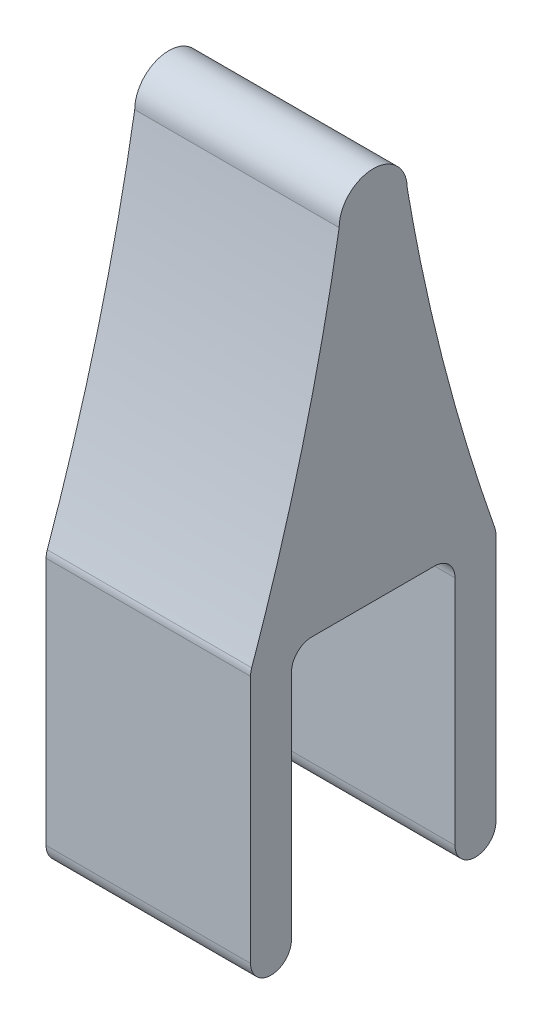
SolidWorks part; units mm, degrees
ref_plane "Front Plane" through (0, 0, 0) normal (0, 0, 1) x (1, 0, 0)
ref_plane "Top Plane" through (0, 0, 0) normal (0, 1, 0) x (1, 0, 0)
ref_plane "Right Plane" through (0, 0, 0) normal (1, 0, 0) x (0, 0, -1)
sketch "Sketch1" plane through (0, 0, 0) normal (1, 0, 0) x (0, 0, -1)
  line L0 (-7.62, 0) -> (-11.43, 0)
  line L1 (-11.43, 0) -> (-11.43, 25.4)
  line L2 (0, -1000) -> (0, 49000) construction
  line L3 (-11.43, 25.4) -> (11.43, 25.4) construction
  line L4 (-7.62, 0) -> (-7.62, 25.4)
  line L5 (-7.62, 25.4) -> (7.62, 25.4)
  line L6 (7.62, 0) -> (7.62, 25.4)
  line L7 (11.43, 0) -> (11.43, 25.4)
  line L8 (7.62, 0) -> (11.43, 0)
  arc A0 (3.175, 57.15) -> (-3.175, 57.15) centre (0, 57.15) ccw
  spline S0 degree 2 poles (-11.43, 25.4) (-5.9489, 40.9005) (-3.175, 57.15) knots 0 0 0 1 1 1
  spline S1 degree 2 poles (11.43, 25.4) (5.9489, 40.9005) (3.175, 57.15) knots 0 0 0 1 1 1
  point P10 (0, 25.4)
  point P12 (0, 25.4)
  point P14 (-8.89, 38.9586)
  point P16 (-6.9566, 46.4492)
  point P18 (-11.0213, 28.9709)
  point P21 (-8.2158, 35.3406)
  dimension "D5" = 6.35
  dimension "D1" = 7.62
  dimension "D2" = 3.81
  dimension "D3" = 25.4
  dimension "D4" = 31.75
  dimension "D6" = 25.4
extrude "Boss-Extrude1" add sketch "Sketch1" along normal blind 19.05
fillet "Fillet2" radius 1.905 8 edges at (9.525, 25.4, -11.43) (9.525, 0, -11.43) (9.525, 0, -7.62) (9.525, 0, 7.62) (9.525, 0, 11.43) (9.525, 25.4, -7.62) (9.525, 25.4, 7.62) (9.525, 25.4, 11.43)
